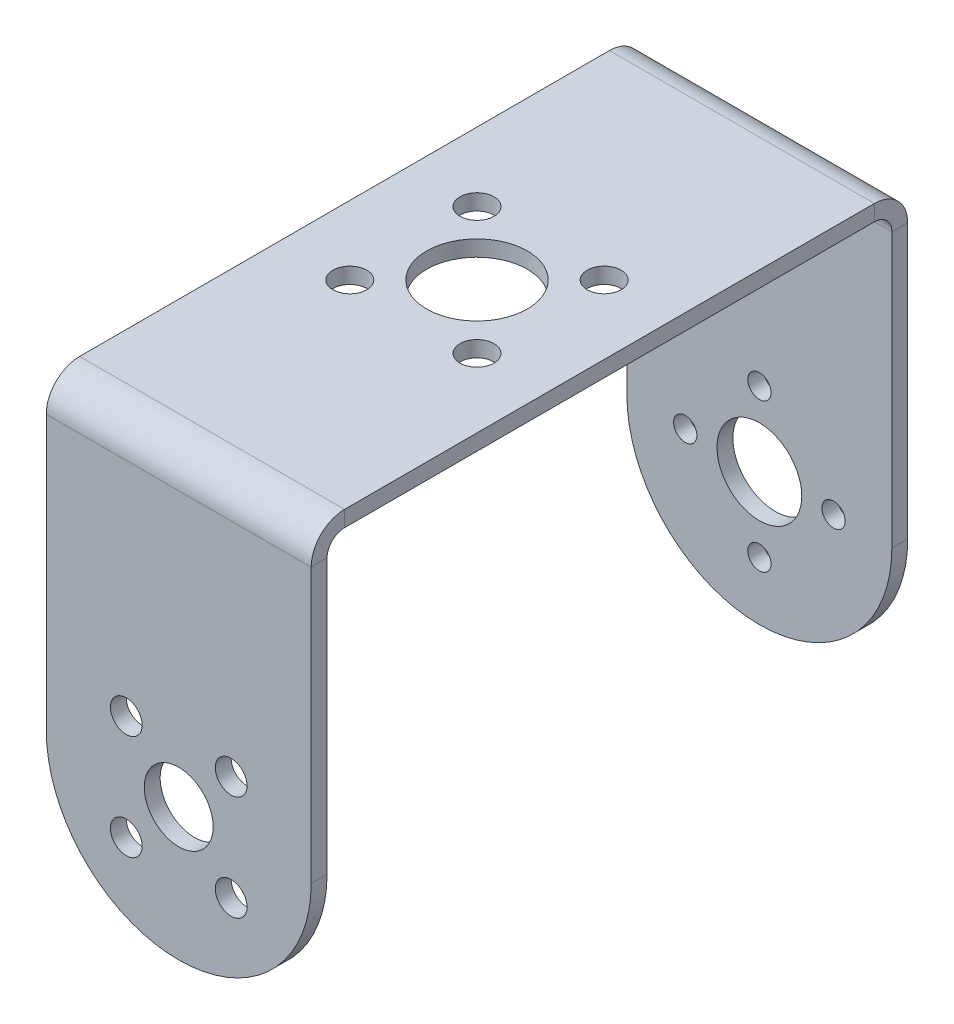
SolidWorks part; units mm, degrees
note: The reader was unsure of these and kept them because the rebuilt part matched: flange length of "Edge-Flange1".
material "1.0037 (S235JR)"
ref_plane "Front Plane" through (0, 0, 0) normal (0, 0, 1) x (1, 0, 0)
ref_plane "Top Plane" through (0, 0, 0) normal (0, 1, 0) x (1, 0, 0)
ref_plane "Right Plane" through (0, 0, 0) normal (1, 0, 0) x (0, 0, -1)
sketch "Sketch1" plane through (0, 0, 0) normal (0, 1, 0) x (1, 0, 0)
  line L1 (12.5, -26.65) -> (-12.5, -26.65)
  line L2 (12.5, -26.65) -> (12.5, 26.65)
  line L3 (12.5, 26.65) -> (-12.5, 26.65)
  line L4 (-12.5, -26.65) -> (-12.5, 26.65)
  line L5 (12.5, -26.65) -> (-12.5, 26.65) construction
  line L6 (12.5, 26.65) -> (-12.5, -26.65) construction
  point P0 (0, 0)
  dimension "D1" = 53.3
  dimension "D2" = 25
base flange "Base-Flange1" sketch "Sketch1" thickness 1.5 reverse thickness direction no parameters "D1"=1.65
edge flange "Edge-Flange1" sketch "Sketch10" flange profiles "Sketch10", "Sketch11" flange angle 90 flange length 40 flange position material outside bend radius 1.65 thickness 1.5 relief rectangular parameters "D1"=2, "D6"=10, "D8"=1
sketch "Sketch10" plane through (0, -1.5, 26.65) normal (0, 0, 1) x (-1, 0, 0)
  line L0 (12.5, 0) -> (-12.5, 0) construction
  line L1 (12.5, 0) -> (-12.5, 0)
  line L2 (-12.5, 0) -> (-12.5, 40)
  line L3 (-12.5, 40) -> (12.5, 40)
  line L4 (12.5, 40) -> (12.5, 0)
sketch "Sketch11" plane through (0, -1.5, -26.65) normal (0, 0, -1) x (1, 0, 0)
  line L0 (12.5, 0) -> (-12.5, 0) construction
  line L1 (12.5, 0) -> (-12.5, 0)
  line L2 (-12.5, 0) -> (-12.5, 40)
  line L3 (-12.5, 40) -> (12.5, 40)
  line L4 (12.5, 40) -> (12.5, 0)
bend "EdgeBend1" bend radius 1.65 bend angle 90 parameters "D5"=1
bend "EdgeBend2" bend radius 1.65 bend angle 90 parameters "D5"=2
sketch "Sketch12" plane through (0, 0, 28.15) normal (0, 0, 1) x (1, 0, 0)
  line L0 (-12.5, -41.5) -> (12.5, -41.5) construction
  line L1 (4.9497, -33.9497) -> (-4.9497, -33.9497) construction
  line L2 (4.9497, -33.9497) -> (4.9497, -24.0503) construction
  line L3 (4.9497, -24.0503) -> (-4.9497, -24.0503) construction
  line L4 (-4.9497, -33.9497) -> (-4.9497, -24.0503) construction
  line L5 (4.9497, -33.9497) -> (-4.9497, -24.0503) construction
  line L6 (4.9497, -24.0503) -> (-4.9497, -33.9497) construction
  circle A0 centre (-4.9497, -24.0503) radius 1.5
  circle A1 centre (4.9497, -24.0503) radius 1.5
  circle A2 centre (-4.9497, -33.9497) radius 1.5
  circle A3 centre (4.9497, -33.9497) radius 1.5
  circle A4 centre (0, -29) radius 3.25
  point P0 (0, -29)
  point P7 (0, -41.5)
  dimension "D3" = 3
  dimension "D4" = 6.5
  dimension "D1" = 14
  dimension "D2" = 12.5
extrude "Cut-Extrude1" cut sketch "Sketch12" against normal up to next normal cut yes
sketch "Sketch13" plane through (0, 0, -28.15) normal (0, 0, -1) x (-1, 0, 0)
  line L0 (0, -29) -> (0, -36) construction
  line L1 (0, -29) -> (-7, -29) construction
  line L2 (0, -29) -> (0, -22) construction
  line L3 (0, -29) -> (7, -29) construction
  circle A0 centre (0, -29) radius 4
  circle A1 centre (0, -36) radius 1.1
  circle A2 centre (-7, -29) radius 1.1
  circle A3 centre (0, -22) radius 1.1
  circle A4 centre (7, -29) radius 1.1
  point P12 (0, -29)
  dimension "D1" = 8
  dimension "D3" = 2.2
  dimension "D2" = 7
  dimension "D4" = 4
extrude "Cut-Extrude2" cut sketch "Sketch13" against normal up to next normal cut yes
fillet "Fillet1" radius 12.5 4 edges at (12.5, -41.5, 27.4) (-12.5, -41.5, 27.4) (-12.5, -41.5, -27.4) (12.5, -41.5, -27.4)
sketch "Sketch14" plane through (0, 0, 0) normal (0, 1, 0) x (1, 0, 0)
  circle A0 centre (0, 0) radius 15
  dimension "D1" = 30
sketch "Sketch17" plane through (0, 0, 0) normal (0, 1, 0) x (1, 0, 0)
  line L1 (6, -6) -> (-6, -6) construction
  line L2 (6, -6) -> (6, 6) construction
  line L3 (6, 6) -> (-6, 6) construction
  line L4 (-6, -6) -> (-6, 6) construction
  line L5 (6, -6) -> (-6, 6) construction
  line L6 (6, 6) -> (-6, -6) construction
  circle A0 centre (-6, 6) radius 1.6
  circle A1 centre (6, 6) radius 1.6
  circle A2 centre (6, -6) radius 1.6
  circle A3 centre (-6, -6) radius 1.6
  circle A4 centre (0, 0) radius 4.75
  point P0 (0, 0)
  dimension "D2" = 3.2
  dimension "D3" = 9.5
  dimension "D1" = 12
extrude "Cut-Extrude3" cut sketch "Sketch17" against normal through all normal cut yes
sketch "Bend-Lines1" [suppressed] plane through (0, 0, 0) normal (0, 1, 0) x (1, 0, 0)
sketch "Bounding-Box1" [suppressed] plane through (0, 0, 0) normal (0, 1, 0) x (1, 0, 0)
sheet metal parameters "Sheet-Metal1" thickness 1.5 parameters "D1"=2
flat pattern "Flat-Pattern1" [suppressed]
sketch "Bend-Lines2" plane through (0, 0, 0) normal (0, 1, 0) x (1, 0, 0)
sketch3d "Bounding-Box2" [suppressed]
  line L0 (10, 26.25, 0) -> (10, -26.25, 0) construction
  line L1 (-10, 26.25, 0) -> (-10, -26.25, 0) construction
  line L2 (10, 26.25, 0) -> (-10, 26.25, 0) construction
  line L3 (10, -26.25, 0) -> (-10, -26.25, 0) construction
sheet metal parameters "Sheet-Metal2" thickness 1.5 parameters "D1"=2
flat pattern "Flat-Pattern1"
sketch "Bend-Lines2" plane through (0, 0, 0) normal (0, 1, 0) x (1, 0, 0)
  line L0 (10, 26.4098) -> (-10, 26.4098) construction
  line L1 (-10, -26.4098) -> (10, -26.4098) construction
  line L2 (10, 26.4098) -> (-10, 26.4098) construction
  line L3 (-10, -26.4098) -> (10, -26.4098) construction
sketch3d "Bounding-Box2" [suppressed]
  line L0 (-10, 46.5697, 0) -> (-10, -46.5697, 0) construction
  line L1 (10, 46.5697, 0) -> (10, -46.5697, 0) construction
  line L2 (-10, 46.5697, 0) -> (10, 46.5697, 0) construction
  line L3 (-10, -46.5697, 0) -> (10, -46.5697, 0) construction
bend of the flat pattern "EdgeBend1>1"
bend of the flat pattern "EdgeBend2>1"
sheet metal parameters "Sheet-Metal3" thickness 1.5 parameters "D1"=2
flat pattern "Flat-Pattern1"
sketch "Bend-Lines2" plane through (0, 0, 0) normal (0, 1, 0) x (1, 0, 0)
  line L0 (10, 26.4098) -> (-10, 26.4098) construction
  line L1 (-10, -26.4098) -> (10, -26.4098) construction
  line L2 (10, 26.4098) -> (-10, 26.4098) construction
  line L3 (-10, -26.4098) -> (10, -26.4098) construction
sketch3d "Bounding-Box2" [suppressed]
  line L0 (-10, 51.5697, 0) -> (-10, -51.5697, 0) construction
  line L1 (10, 51.5697, 0) -> (10, -51.5697, 0) construction
  line L2 (-10, 51.5697, 0) -> (10, 51.5697, 0) construction
  line L3 (-10, -51.5697, 0) -> (10, -51.5697, 0) construction
bend of the flat pattern "EdgeBend1>1"
bend of the flat pattern "EdgeBend2>1"
sheet metal parameters "Sheet-Metal4" thickness 1.5 parameters "D1"=2
flat pattern "Flat-Pattern1"
sketch "Bend-Lines2" plane through (0, 0, 0) normal (0, 1, 0) x (1, 0, 0)
  line L0 (12.5, 26.4098) -> (-12.5, 26.4098) construction
  line L1 (-12.5, -26.4098) -> (12.5, -26.4098) construction
  line L2 (12.5, 26.4098) -> (-12.5, 26.4098) construction
  line L3 (-12.5, -26.4098) -> (12.5, -26.4098) construction
sketch3d "Bounding-Box2" [suppressed]
  line L0 (-12.5, 71.5696, 0) -> (-12.5, -71.5696, 0) construction
  line L1 (12.5, 71.5696, 0) -> (12.5, -71.5696, 0) construction
  line L2 (-12.5, 71.5696, 0) -> (12.5, 71.5696, 0) construction
  line L3 (-12.5, -71.5696, 0) -> (12.5, -71.5696, 0) construction
bend of the flat pattern "EdgeBend1>1"
bend of the flat pattern "EdgeBend2>1"
sheet metal parameters "Sheet-Metal6" thickness 1.5 parameters "D1"=2
flat pattern "Flat-Pattern1"
sketch "Bend-Lines2" plane through (0, 0, 0) normal (0, 1, 0) x (1, 0, 0)
  line L0 (12.5, 26.885) -> (-12.5, 26.885) construction
  line L1 (-12.5, -26.885) -> (12.5, -26.885) construction
  line L2 (12.5, 26.885) -> (-12.5, 26.885) construction
  line L3 (-12.5, -26.885) -> (12.5, -26.885) construction
sketch3d "Bounding-Box2" [suppressed]
  line L0 (-12.5, 67.1199, 0) -> (-12.5, -67.1199, 0) construction
  line L1 (12.5, 67.1199, 0) -> (12.5, -67.1199, 0) construction
  line L2 (-12.5, 67.1199, 0) -> (12.5, 67.1199, 0) construction
  line L3 (-12.5, -67.1199, 0) -> (12.5, -67.1199, 0) construction
bend of the flat pattern "EdgeBend2>2"
bend of the flat pattern "EdgeBend1>2"
